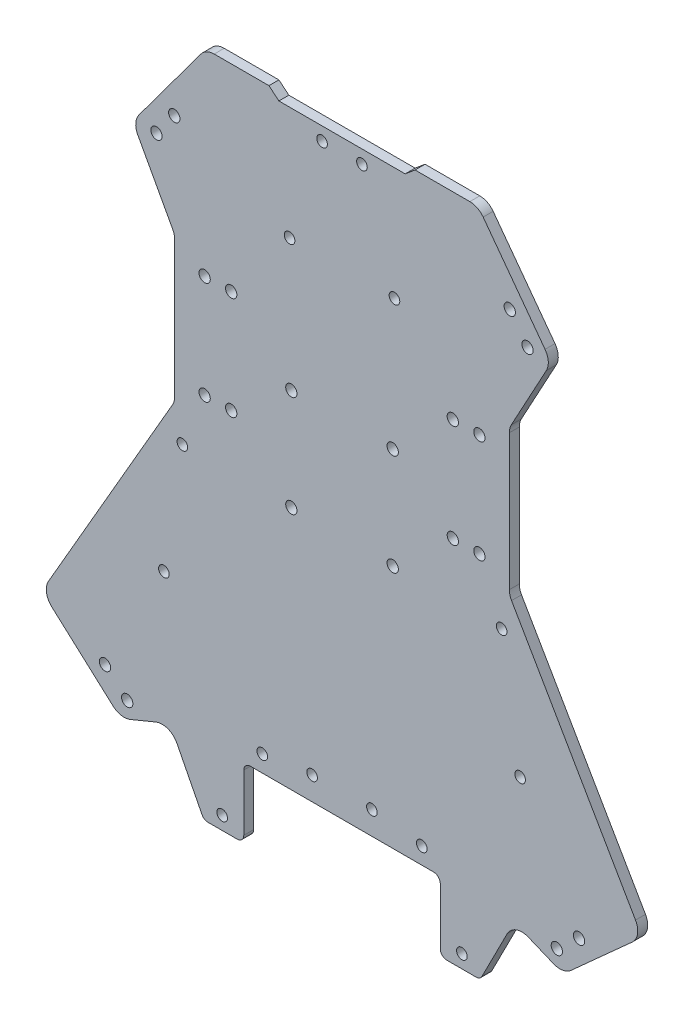
SolidWorks part; units mm, degrees
material "Thornel Mat VMA"
ref_plane "Front Plane" through (0, 0, 0) normal (0, 0, 1) x (1, 0, 0)
ref_plane "Top Plane" through (0, 0, 0) normal (0, 1, 0) x (1, 0, 0)
ref_plane "Right Plane" through (0, 0, 0) normal (1, 0, 0) x (0, 0, -1)
sketch "Sketch1" plane through (0, 0, 0) normal (0, 0, 1) x (1, 0, 0)
  line L0 (0, 0) -> (19, 0)
  line L1 (19, 0) -> (21.9794, 2.5)
  line L2 (21.9794, 2.5) -> (40.9794, 2.5)
  line L3 (40.9794, 2.5) -> (62.9878, -27.2427)
  line L4 (62.9878, -27.2427) -> (50.3431, -50.5314)
  line L5 (50.3431, -50.5314) -> (50.3431, -94.0314)
  line L6 (50.3431, -94.0314) -> (90.3431, -163.3134)
  line L7 (90.3431, -163.3134) -> (66.5625, -184.7256)
  line L8 (66.5625, -184.7256) -> (51.7804, -178.6026)
  line L9 (51.7804, -178.6026) -> (41.5656, -198.6503)
  line L10 (41.5656, -198.6503) -> (29.5656, -198.6503)
  line L11 (29.5656, -198.6503) -> (29.5656, -177.6503)
  line L12 (29.5656, -177.6503) -> (0, -177.6503)
  line L14 (0, 0) -> (0, -177.6503)
  line L15 (15.7785, -34.0523) -> (29.2258, -52.2253) construction
  line L16 (29.2258, -52.2253) -> (62.9878, -27.2427) construction
  line L17 (53.5911, -139.8884) -> (62.2396, -132.1013) construction
  line L18 (62.2396, -132.1013) -> (90.3431, -163.3134) construction
  circle A0 centre (6, -4) radius 1.6
  circle A7 centre (48.0431, -104.0476) radius 1.6
  circle A10 centre (53.5911, -139.8884) radius 1.6
  circle A11 centre (36.0656, -194.6503) radius 1.6
  circle A12 centre (24, -172.6503) radius 1.6
  circle A13 centre (9, -170.6503) radius 1.6
  circle A14 centre (15.7785, -34.0523) radius 1.6
  dimension "D20" = 3.2
  dimension "D40" = 3.2
  dimension "D43" = 3.2
  dimension "D46" = 3.2
  dimension "D55" = 3.2
  dimension "D57" = 3.2
  dimension "D58" = 3.2
  dimension "D2" = 2.5
  dimension "D3" = 140
  dimension "D4" = 19
  dimension "D5" = 126.5
  dimension "D6" = 37
  dimension "D7" = 115
  dimension "D8" = 26.5
  dimension "D9" = 43.5
  dimension "D10" = 150
  dimension "D11" = 80
  dimension "D12" = 102
  dimension "D13" = 32
  dimension "D14" = 115.5
  dimension "D15" = 16
  dimension "D16" = 94.5
  dimension "D17" = 22.5
  dimension "D18" = 12
  dimension "D19" = 21
  dimension "D21" = 19
  dimension "D22" = 4
  dimension "D23" = 6
  dimension "D24" = 22.6073
  dimension "D25" = 42
  dimension "D26" = 11.6377
  dimension "D27" = 42
  dimension "D41" = 7
  dimension "D42" = 2.3
  dimension "D53" = 4
  dimension "D54" = 6.5
  dimension "D56" = 5
  dimension "D59" = 9
  dimension "D60" = 7
  dimension "D61" = 24
extrude "Boss-Extrude1" add sketch "Sketch1" along normal blind 3 contours L14 L12 L11 L10 L9 L8 L7 L6 L5 L4 L3 L2 L1 L0
extrude "Cut-Extrude1" cut sketch "Sketch1<3>" along normal through all contours A0 | A14 | A7 | A10 | A12 | A13 | A11
sketch "Sketch1<3>" plane through (0, 0, 0) normal (0, 0, 1) x (1, 0, 0) same geometry as "Sketch1"
hole_wizard "MntPatt-Lndgear" positions "Sketch2" profile "Sketch3" hole size "M3" standard "ANSI Metric" end condition up to next
sketch "Sketch2" plane through (0, 0, 3) normal (0, 0, 1) x (1, 0, 0)
  line L1 (33.3431, -56.8326) -> (41.3431, -56.8326) construction
  line L2 (33.3431, -56.8326) -> (33.3431, -87.8326) construction
  line L3 (33.3431, -87.8326) -> (41.3431, -87.8326) construction
  line L4 (41.3431, -56.8326) -> (41.3431, -87.8326) construction
  line L5 (41.3431, -87.8326) -> (33.3431, -56.8326) construction
  line L7 (33.3431, -87.8326) -> (41.3431, -56.8326) construction
  line L9 (40.9794, 2.5) -> (62.9878, -27.2427) construction
  line L10 (50.3431, -50.5314) -> (50.3431, -94.0314) construction
  point P0 (33.3431, -56.8326)
  point P3 (41.3431, -56.8326)
  point P6 (33.3431, -87.8326)
  point P9 (41.3431, -87.8326)
  dimension "D1" = 8
  dimension "D2" = 31
  dimension "D3" = 35
  dimension "D4" = 9
sketch "Sketch3" plane through (33.3431, -56.8326, 3) normal (1, 0, 0) x (0, -1, 0)
  line L0 (0, 0) -> (0, 3.001)
  line L1 (0, 3.001) -> (1.7, 3.001)
  line L2 (1.7, 3.001) -> (1.7, 0)
  line L5 (1.7, 0) -> (0, 0)
  line L11 (0, -6.35) -> (0, 107.95) construction
  dimension "Thru Hole Dia." = 3.4
  dimension "Thru Hole Depth" = 3.001
hole_wizard "MntPatt-RearArm" positions "Sketch4" profile "Sketch5" hole size "M3" standard "ANSI Metric" end condition up to next
sketch "Sketch4" plane through (0, 0, 3) normal (0, 0, 1) x (1, 0, 0)
  line L0 (50.4727, -19.5759) -> (55.8261, -26.8106) construction
  line L2 (40.9794, 2.5) -> (62.9878, -27.2427) construction
  line L4 (62.9878, -27.2427) -> (50.3431, -50.5314) construction
  point P0 (55.8261, -26.8106)
  point P3 (50.4727, -19.5759)
  dimension "D1" = 9
  dimension "D2" = 5.5
  dimension "D3" = 6.5
sketch "Sketch5" plane through (55.8261, -26.8106, 3) normal (1, 0, 0) x (0, -1, 0)
  line L0 (0, 0) -> (0, 3.001)
  line L1 (0, 3.001) -> (1.7, 3.001)
  line L2 (1.7, 3.001) -> (1.7, 0)
  line L5 (1.7, 0) -> (0, 0)
  line L11 (0, -6.35) -> (0, 107.95) construction
  dimension "Thru Hole Dia." = 3.4
  dimension "Thru Hole Depth" = 3.001
hole_wizard "MntPatt_ForeArm" positions "Sketch6" profile "Sketch7" hole size "M3" standard "ANSI Metric" end condition up to next
sketch "Sketch6" plane through (0, 0, 3) normal (0, 0, 1) x (1, 0, 0)
  line L0 (64.6378, -179.0576) -> (71.3261, -173.0354) construction
  line L2 (66.5625, -184.7256) -> (51.7804, -178.6026) construction
  line L3 (90.3431, -163.3134) -> (66.5625, -184.7256) construction
  point P0 (71.3261, -173.0354)
  point P3 (64.6378, -179.0576)
  dimension "D1" = 4.5
  dimension "D2" = 5.5
  dimension "D3" = 9
sketch "Sketch7" plane through (71.3261, -173.0354, 3) normal (1, 0, 0) x (0, -1, 0)
  line L0 (0, 0) -> (0, 3.001)
  line L1 (0, 3.001) -> (1.7, 3.001)
  line L2 (1.7, 3.001) -> (1.7, 0)
  line L5 (1.7, 0) -> (0, 0)
  line L11 (0, -6.35) -> (0, 107.95) construction
  dimension "Thru Hole Dia." = 3.4
  dimension "Thru Hole Depth" = 3.001
mirror "Mirror2" about plane through (0, 0, 3) normal (1, 0, 0) of "MntPatt_ForeArm", "MntPatt-RearArm", "Cut-Extrude1", "Boss-Extrude1", "MntPatt-Lndgear"
fillet "Fillet1" radius 5 14 edges at (40.9794, 2.5, 1.5) (-40.9794, 2.5, 1.5) (51.7804, -178.6026, 1.5) (66.5625, -184.7256, 1.5) (-51.7804, -178.6026, 1.5) (-66.5625, -184.7256, 1.5) (90.3431, -163.3134, 1.5) (-90.3431, -163.3134, 1.5) (50.3431, -94.0314, 1.5) (-50.3431, -94.0314, 1.5) (50.3431, -50.5314, 1.5) (-50.3431, -50.5314, 1.5) (62.9878, -27.2427, 1.5) (-62.9878, -27.2427, 1.5)
fillet "Fillet2" radius 2 6 edges at (-41.5656, -198.6503, 1.5) (-29.5656, -198.6503, 1.5) (-29.5656, -177.6503, 1.5) (29.5656, -177.6503, 1.5) (29.5656, -198.6503, 1.5) (41.5656, -198.6503, 1.5)
hole_wizard "M3 Clearance Hole4" positions "Sketch8" profile "Sketch9" hole size "M3" standard "ANSI Metric" end condition up to next
sketch "Sketch8" plane through (0, 0, 3) normal (0, 0, 1) x (1, 0, 0)
  line L1 (-15.25, -73.5751) -> (15.25, -73.5751) construction
  line L2 (-15.25, -73.5751) -> (-15.25, -104.0751) construction
  line L3 (-15.25, -104.0751) -> (15.25, -104.0751) construction
  line L4 (15.25, -73.5751) -> (15.25, -104.0751) construction
  line L5 (0, -177.6503) -> (0, 0) construction
  line L6 (27.5656, -177.6503) -> (-27.5656, -177.6503) construction
  line L8 (-15.25, -73.5751) -> (15.25, -104.0751) construction
  point P0 (-15.25, -73.5751)
  point P2 (15.25, -73.5751)
  point P4 (15.25, -104.0751)
  point P6 (-15.25, -104.0751)
  point P116 (0, -73.5751)
  point P122 (0, -88.8251)
  dimension "D1" = 30.5
sketch "Sketch9" plane through (-15.25, -73.5751, 3) normal (1, 0, 0) x (0, -1, 0)
  line L0 (0, 0) -> (0, 3)
  line L1 (0, 3) -> (1.7, 3)
  line L2 (1.7, 3) -> (1.7, 0)
  line L5 (1.7, 0) -> (0, 0)
  line L11 (0, -6.35) -> (0, 107.95) construction
  dimension "Thru Hole Dia." = 3.4
  dimension "Thru Hole Depth" = 3
equation "\"ArmBraceSpacing\"= 9"
equation "\"D3@Sketch6\"=\"ArmBraceSpacing\""
equation "\"D1@Sketch4\"=\"ArmBraceSpacing\""
